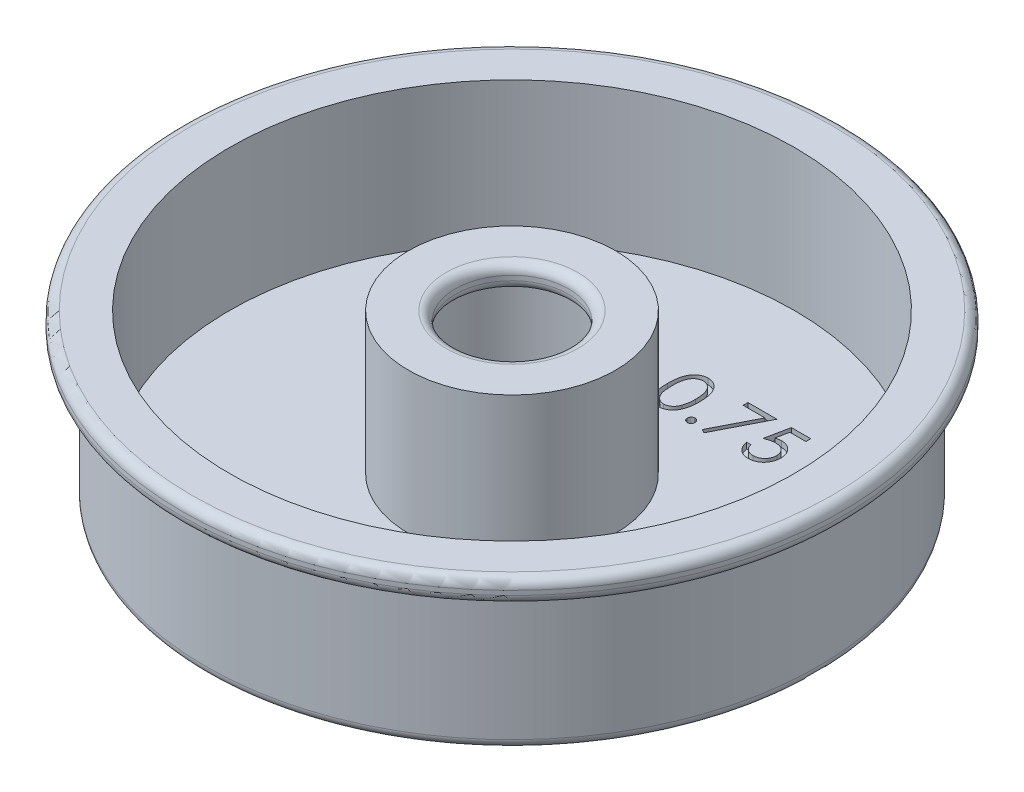
SolidWorks part; units mm, degrees
ref_plane "Front Plane" through (0, 0, 0) normal (0, 0, 1) x (1, 0, 0)
ref_plane "Top Plane" through (0, 0, 0) normal (0, 1, 0) x (1, 0, 0)
ref_plane "Right Plane" through (0, 0, 0) normal (1, 0, 0) x (0, 0, -1)
sketch "Sketch1" plane through (0, 0, 0) normal (0, 0, 1) x (1, 0, 0)
  line L0 (0, 0) -> (0, 11.1543)
  line L3 (13.97, 15.9118) -> (13.97, -3.1382)
  line L4 (13.97, -3.1382) -> (38.1, -3.1382)
  line L5 (38.1, -3.1382) -> (38.1, 15.9118)
  line L8 (40.005, -6.3132) -> (12.065, -6.3132)
  line L9 (41.275, -5.0432) -> (41.275, 11.5037)
  line L10 (42.545, 12.7737) -> (43.18, 12.7737)
  line L11 (44.45, 14.0437) -> (44.45, 14.6418)
  line L12 (38.1, 15.9118) -> (43.18, 15.9118)
  line L13 (13.97, 15.9118) -> (8.89, 15.9118)
  line L14 (7.62, 14.6418) -> (7.62, 14.0068)
  line L15 (10.795, -5.0432) -> (10.795, 11.4668)
  line L16 (9.525, 12.7368) -> (8.89, 12.7368)
  arc A0 (43.18, 15.9118) -> (44.45, 14.6418) centre (43.18, 14.6418) cw
  arc A1 (44.45, 14.0437) -> (43.18, 12.7737) centre (43.18, 14.0437) cw
  arc A2 (42.545, 12.7737) -> (41.275, 11.5037) centre (42.545, 11.5037) ccw
  arc A3 (41.275, -5.0432) -> (40.005, -6.3132) centre (40.005, -5.0432) cw
  arc A4 (12.065, -6.3132) -> (10.795, -5.0432) centre (12.065, -5.0432) cw
  arc A5 (10.795, 11.4668) -> (9.525, 12.7368) centre (9.525, 11.4668) ccw
  arc A6 (8.89, 12.7368) -> (7.62, 14.0068) centre (8.89, 14.0068) cw
  arc A7 (7.62, 14.6418) -> (8.89, 15.9118) centre (8.89, 14.6418) cw
  dimension "D10" = 1.27
  dimension "D1" = 3.175
  dimension "D2" = 6.35
  dimension "D3" = 3.175
  dimension "D4" = 6.35
  dimension "D5" = 3.175
  dimension "D6" = 13.97
  dimension "D7" = 38.1
  dimension "D8" = 3.1382
  dimension "D9" = 3.175
  dimension "D11" = 19.05
  dimension "D12" = 19.05
revolve "Revolve2" add sketch "Sketch1" angle 360 about L0 region at (13.5398, 6.3868, 0)
sketch "Sketch2" plane through (0, -3.1382, 0) normal (0, 1, 0) x (1, 0, 0)
  text T0 "3 x 0.75" font "Century Gothic" height in points 24
  point P1 (-14.2897, 17.8622)
  point P2 (0, 0)
  point P3 (0, 0)
extrude "Cut-Extrude1" cut sketch "Sketch2" against normal blind 0.7937
